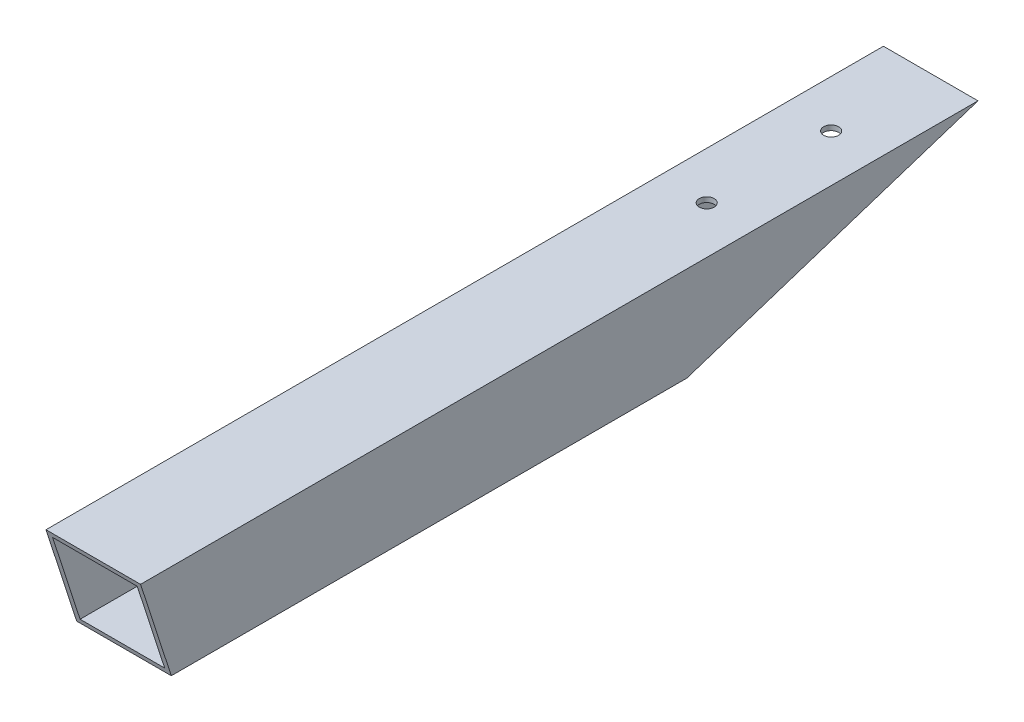
SolidWorks part; units mm, degrees
ref_plane "Plano frontal" through (0, 0, 0) normal (0, 0, 1) x (1, 0, 0)
ref_plane "Plano superior" through (0, 0, 0) normal (0, 1, 0) x (1, 0, 0)
ref_plane "Plano direito" through (0, 0, 0) normal (1, 0, 0) x (0, 0, -1)
sketch "Esboço1" plane through (0, 0, 0) normal (0, 0, 1) x (1, 0, 0)
  line L1 (-9.5, 9.5) -> (9.5, 9.5)
  line L2 (-9.5, 9.5) -> (-9.5, -9.5)
  line L3 (-9.5, -9.5) -> (9.5, -9.5)
  line L4 (9.5, 9.5) -> (9.5, -9.5)
  line L5 (-9.5, 9.5) -> (9.5, -9.5) construction
  line L6 (-9.5, -9.5) -> (9.5, 9.5) construction
  line L11 (-5.6574, 5.6574) -> (5.6574, -5.6574) construction
  line L12 (-5.6574, -5.6574) -> (5.6574, 5.6574) construction
  point P0 (0, 0)
  point P6 (0, 0)
  dimension "D1" = 19
extrude "Ressalto-extrusão1" add sketch "Esboço1" along normal blind 260
shell "Casca2" thickness 1 removed face at (0, 0, 0) removed face at (0, 0, 260)
sketch "Esboço2" plane through (9.5, 0, 0) normal (1, 0, 0) x (0, 0, -1)
  line L0 (0, 9.5) -> (-58.476, -9.5)
  line L1 (-260, -9.5) -> (0, -9.5) construction
  line L4 (-260, 9.5) -> (0, 9.5) construction
  line L5 (-58.476, -9.5) -> (0, -9.5)
  line L7 (0, -9.5) -> (0, 9.5)
  dimension "D1" = 18
extrude "Corte-extrusão1" cut sketch "Esboço2" against normal through all
sketch "Esboço4" plane through (9.5, 0, 0) normal (1, 0, 0) x (0, 0, -1)
  line L0 (-168.5503, 10.4737) -> (-161.2895, -11.8728)
  line L1 (-161.2895, -11.8728) -> (-264.8128, -45.5096)
  line L2 (-264.8128, -45.5096) -> (-289.0578, 22.1497)
  line L3 (-289.0578, 22.1497) -> (-184.5161, 59.6112)
  line L4 (-184.5161, 59.6112) -> (-168.5503, 10.4737)
extrude "Corte-extrusão3" cut sketch "Esboço4" against normal through all
sketch "Esboço5" plane through (0, 9.5, 0) normal (0, 1, 0) x (1, 0, 0)
  circle A0 centre (0, -20) radius 1.5
  circle A1 centre (0, -45) radius 1.5
  dimension "D3" = 3
  dimension "D1" = 20
  dimension "D2" = 25
extrude "Corte-extrusão4" cut sketch "Esboço5" against normal through all
